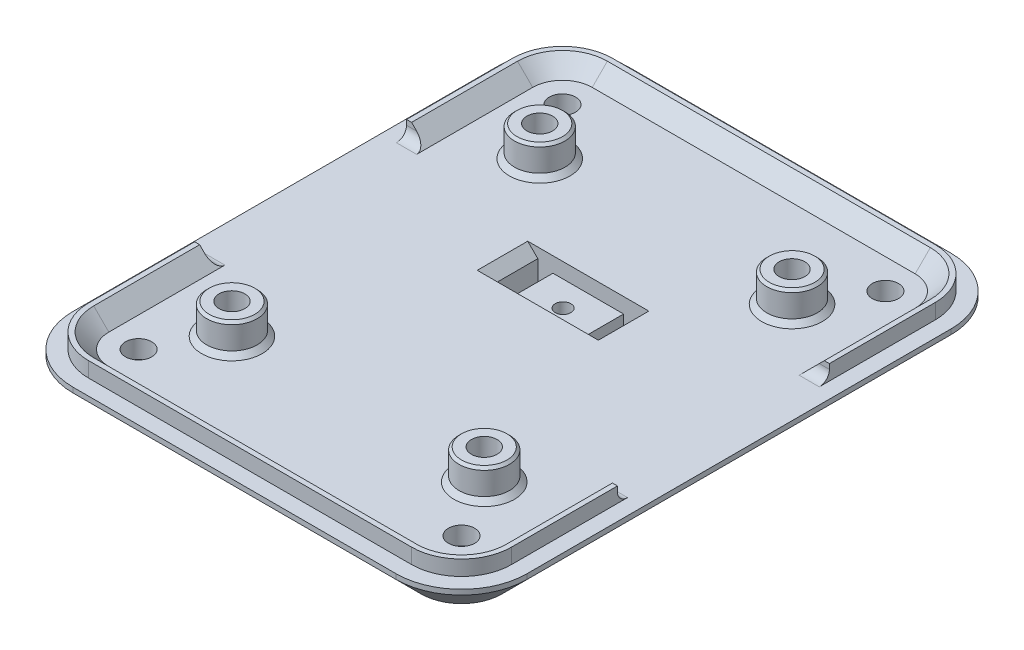
SolidWorks part; units mm, degrees
ref_plane "Front Plane" through (0, 0, 0) normal (0, 0, 1) x (1, 0, 0)
ref_plane "Top Plane" through (0, 0, 0) normal (0, 1, 0) x (1, 0, 0)
ref_plane "Right Plane" through (0, 0, 0) normal (1, 0, 0) x (0, 0, -1)
sketch "Sketch1" plane through (0, 0, 0) normal (0, 1, 0) x (1, 0, 0)
  line L0 (-32, -55) -> (32, -55)
  line L1 (-45, -42) -> (-45, 42)
  line L2 (-32, 55) -> (32, 55)
  line L3 (45, -42) -> (45, 42)
  arc A0 (-32, -55) -> (-45, -42) centre (-32, -42) cw
  arc A1 (32, -55) -> (45, -42) centre (32, -42) ccw
  arc A2 (32, 55) -> (45, 42) centre (32, 42) cw
  arc A3 (-45, 42) -> (-32, 55) centre (-32, 42) cw
extrude "Boss-Extrude1" add sketch "Sketch1" along normal blind 6
chamfer "Chamfer1" distance 5 angle 45 8 edges at (0, 0, -55) (-41.1924, 0, -51.1924) (41.1924, 0, -51.1924) (-45, 0, 0) (45, 0, 0) (-41.1924, 0, 51.1924) (41.1924, 0, 51.1924) (0, 0, 55)
sketch "Sketch2" plane through (0, 6, 0) normal (0, 1, 0) x (1, 0, 0)
  line L16 (41.9, -21) -> (41.9, -42)
  line L17 (32, -51.9) -> (-32, -51.9)
  line L18 (-41.9, -42) -> (-41.9, -21)
  line L19 (-41.9, -21) -> (-37.9, -21)
  line L20 (37.9, -21) -> (37.9, -42)
  line L21 (32, -47.9) -> (-32, -47.9)
  line L22 (-37.9, -42) -> (-37.9, -21)
  line L23 (-37.9, -25) -> (-37.9, -25)
  line L24 (37.9, -21) -> (41.9, -21)
  line L25 (0, 0) -> (14.5722, 0) construction
  line L26 (-37.9, -42) -> (-37.9, -25) construction
  line L27 (32, 47.9) -> (-32, 47.9)
  line L28 (37.9, 21) -> (37.9, 42)
  line L29 (37.9, 21) -> (41.9, 21)
  line L30 (41.9, 21) -> (41.9, 42)
  line L31 (32, 51.9) -> (-32, 51.9)
  line L32 (-41.9, 42) -> (-41.9, 21)
  line L33 (-41.9, 21) -> (-37.9, 21)
  line L34 (-37.9, 42) -> (-37.9, 21)
  arc A8 (32, -51.9) -> (41.9, -42) centre (32, -42) ccw
  arc A9 (-41.9, -42) -> (-32, -51.9) centre (-32, -42) ccw
  arc A10 (32, -47.9) -> (37.9, -42) centre (32, -42) ccw
  arc A11 (-37.9, -42) -> (-32, -47.9) centre (-32, -42) ccw
  arc A12 (-37.9, 42) -> (-32, 47.9) centre (-32, 42) cw
  arc A13 (32, 47.9) -> (37.9, 42) centre (32, 42) cw
  arc A14 (32, 51.9) -> (41.9, 42) centre (32, 42) cw
  arc A15 (-41.9, 42) -> (-32, 51.9) centre (-32, 42) cw
  dimension "D1" = 4
  dimension "D2" = 4
extrude "Boss-Extrude2" add sketch "Sketch2" along normal blind 3 contours A11 L22 L19 L18 A9 L17 A8 L16 L24 L20 A10 L21 | A15 L32 L33 L34 A12 L27 A13 L28 L29 L30 A14 L31 region at (41.0068, 6, 31.5) region at (0, 6, -48.7932)
chamfer "Chamfer2" distance 3 angle 45 10 edges at (37.9, 9, 31.5) (36.1719, 9, 46.1719) (0, 9, 47.9) (-36.1719, 9, 46.1719) (-37.9, 9, 31.5) (-37.9, 9, -31.5) (-36.1719, 9, -46.1719) (0, 9, -47.9) (36.1719, 9, -46.1719) (37.9, 9, -31.5)
sketch "Sketch3" plane through (0, 6, 0) normal (0, 1, 0) x (1, 0, 0)
  line L0 (0, 0) -> (0, 8.9502) construction
  line L1 (-75, -20) -> (75, -20) construction
  line L2 (-75, -20) -> (-75, 20) construction
  line L3 (-75, 20) -> (75, 20) construction
  line L4 (75, -20) -> (75, 20) construction
  line L5 (-75, -20) -> (75, 20) construction
  line L6 (-75, 20) -> (75, -20) construction
  line L7 (28.7581, 0) -> (-28.7581, 0) construction
  circle A0 centre (-25, 30.5) radius 12 construction
  circle A1 centre (-25, 30.5) radius 10.5 construction
  circle A2 centre (-25, 30.5) radius 2.55
  circle A3 centre (25, 30.5) radius 2.55
  circle A4 centre (25, -30.5) radius 2.55
  circle A5 centre (-25, -30.5) radius 2.55
  point P0 (0, 0)
  point P15 (0, 0)
  dimension "D3" = 24
  dimension "D4" = 25
  dimension "D5" = 21
  dimension "D6" = 10.5
  dimension "D7" = 5.1
  dimension "D1" = 40
  dimension "D2" = 150
extrude "Cut-Extrude1" cut sketch "Sketch3" against normal through all
sketch "Sketch4" plane through (0, 6, 0) normal (0, 1, 0) x (1, 0, 0)
  circle A0 centre (-25, 30.5) radius 2.55
  circle A1 centre (25, 30.5) radius 2.55
  circle A2 centre (25, -30.5) radius 2.55
  circle A3 centre (-25, -30.5) radius 2.55
  circle A4 centre (-25, -30.5) radius 5
  circle A5 centre (25, -30.5) radius 5
  circle A6 centre (-25, 30.5) radius 5
  circle A7 centre (25, 30.5) radius 5
  dimension "D1" = 10
extrude "Boss-Extrude3" add sketch "Sketch4" along normal blind 6
chamfer "Chamfer3" distance 1 angle 45 4 edges at (25, 6, 25.5) (-25, 6, 25.5) (-25, 6, -35.5) (25, 6, -35.5)
chamfer "Chamfer4" distance 0.5 angle 45 4 edges at (25, 12, 35.5) (-25, 12, 35.5) (-25, 12, -25.5) (25, 12, -25.5)
sketch "Sketch5" plane through (0, 0, 0) normal (0, -1, 0) x (1, 0, 0)
  circle A0 centre (-25, 30.5) radius 4.1
  circle A1 centre (25, 30.5) radius 4.1
  circle A2 centre (-25, -30.5) radius 4.1
  circle A3 centre (25, -30.5) radius 4.1
  dimension "D1" = 8.2
extrude "Cut-Extrude2" cut sketch "Sketch5" against normal blind 5
sketch "Sketch6" plane through (0, 6, 0) normal (0, 1, 0) x (1, 0, 0)
  line L0 (-32, 42) -> (32, 42) construction
  line L1 (-32, 42) -> (-32, -42) construction
  line L2 (-32, -42) -> (32, -42) construction
  line L3 (32, 42) -> (32, -42) construction
  circle A0 centre (-32, 42) radius 2.6
  circle A1 centre (32, 42) radius 2.6
  circle A2 centre (32, -42) radius 2.6
  circle A3 centre (-32, -42) radius 2.6
  dimension "D1" = 5.2
extrude "Cut-Extrude3" cut sketch "Sketch6" against normal blind 10
sketch "Sketch7" plane through (0, 0, 0) normal (0, -1, 0) x (1, 0, 0)
  circle A0 centre (32, 42) radius 5
  circle A1 centre (-32, 42) radius 5
  circle A2 centre (-32, -42) radius 5
  circle A3 centre (32, -42) radius 5
  dimension "D1" = 10
extrude "Cut-Extrude4" cut sketch "Sketch7" against normal blind 2.8 draft 45
fillet "Fillet1" radius 2 4 edges at (-39.9, 6, 21) (-39.9, 6, -21) (39.9, 6, -21) (39.9, 6, 21)
sketch "Sketch8" plane through (0, 0, 0) normal (0, -1, 0) x (1, 0, 0)
  line L1 (-10, -5.1163) -> (10, -5.1163)
  line L2 (-10, -5.1163) -> (-10, -15.1163)
  line L3 (-10, -15.1163) -> (10, -15.1163)
  line L4 (10, -5.1163) -> (10, -15.1163)
  line L5 (32, -55) -> (-32, -55) construction
  line L6 (-45, -42) -> (-45, 42) construction
  dimension "D1" = 10
  dimension "D2" = 20
  dimension "D3" = 39.8837
  dimension "D4" = 35
extrude "Cut-Extrude5" cut sketch "Sketch8" against normal blind 10 from offset 3 offset against normal yes
chamfer "Chamfer5" distance 2 angle 45 2 edges at (10, 6, -10.1163) (-10, 6, -10.1163)
sketch "Sketch9" plane through (0, 3, 0) normal (0, 1, 0) x (1, 0, 0)
  line L5 (12, 5.1163) -> (-12, 5.1163) construction
  line L6 (0, 5.1163) -> (0, 15.1163) construction
  line L7 (-10, 15.1163) -> (10, 15.1163) construction
  line L12 (-10, 15.1163) -> (-10, 5.1163)
  line L13 (-10, 15.1163) -> (-7, 15.1163)
  line L14 (-7, 15.1163) -> (-7, 5.1163)
  line L15 (-10, 5.1163) -> (-7, 5.1163)
  line L16 (10, 15.1163) -> (7, 15.1163)
  line L17 (7, 15.1163) -> (7, 5.1163)
  line L18 (10, 5.1163) -> (7, 5.1163)
  line L19 (10, 15.1163) -> (10, 5.1163)
  circle A0 centre (0, 10.1163) radius 1.55
  dimension "D3" = 3.1
extrude "Cut-Extrude6" cut sketch "Sketch9" against normal blind 10
